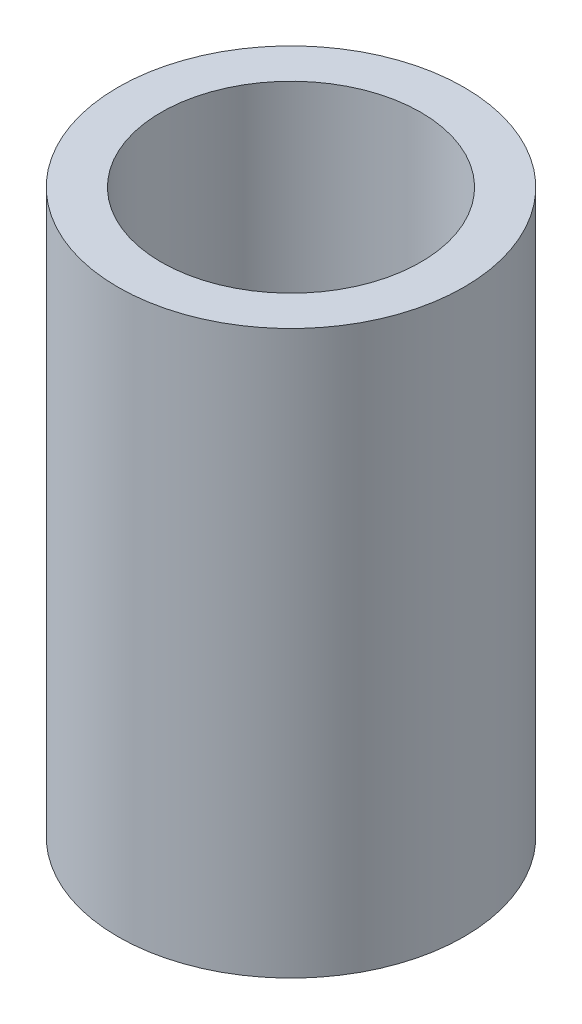
SolidWorks part; units mm, degrees
ref_plane "Front Plane" through (0, 0, 0) normal (0, 0, 1) x (1, 0, 0)
ref_plane "Top Plane" through (0, 0, 0) normal (0, 1, 0) x (1, 0, 0)
ref_plane "Right Plane" through (0, 0, 0) normal (1, 0, 0) x (0, 0, -1)
sketch "Sketch1" plane through (0, 0, 0) normal (0, 1, 0) x (1, 0, 0)
  circle A0 centre (0, 0) radius 12.7
  circle A1 centre (0, 0) radius 9.525
  dimension "D1" = 19.05
  dimension "D2" = 25.4
extrude "Boss-Extrude2" add sketch "Sketch1" along normal blind 41.275
